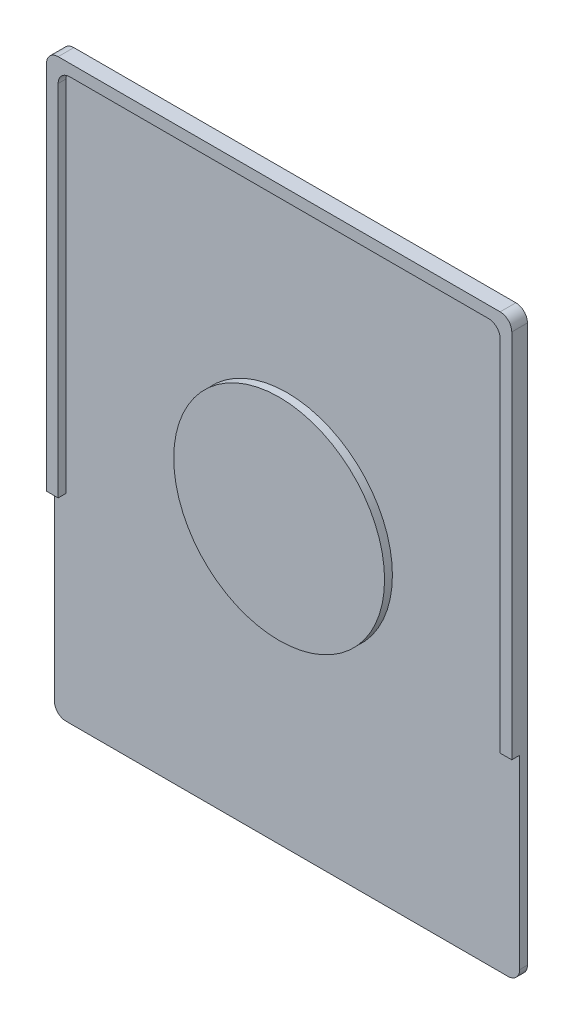
SolidWorks part; units mm, degrees
ref_plane "Front Plane" through (0, 0, 0) normal (0, 0, 1) x (1, 0, 0)
ref_plane "Top Plane" through (0, 0, 0) normal (0, 1, 0) x (1, 0, 0)
ref_plane "Right Plane" through (0, 0, 0) normal (1, 0, 0) x (0, 0, -1)
sketch "Sketch1" plane through (0, 0, 0) normal (0, 0, 1) x (1, 0, 0)
  line L0 (75.9955, -3.6817) -> (75.9955, 195.6023) construction
  line L1 (-0.0045, -3.6817) -> (151.9955, -3.6817)
  line L2 (-4.0045, 0.3183) -> (-4.0045, 191.6023)
  line L3 (-0.0045, 195.6023) -> (151.9955, 195.6023)
  line L4 (155.9955, 0.3183) -> (155.9955, 191.6023)
  line L5 (-4.0045, 95.9603) -> (155.9955, 95.9603) construction
  line L6 (-4.0045, 64.1756) -> (-4.0045, 191.6023)
  line L7 (-0.0045, 195.6023) -> (151.9955, 195.6023)
  line L8 (155.9955, 191.6023) -> (155.9955, 64.1756)
  line L9 (-4.0045, 64.1756) -> (-0.0045, 64.1756)
  line L10 (-0.0045, 64.1756) -> (-0.0045, 187.6023)
  line L11 (3.9955, 191.6023) -> (147.9955, 191.6023)
  line L12 (151.9955, 187.6023) -> (151.9955, 64.1756)
  line L13 (151.9955, 64.1756) -> (155.9955, 64.1756)
  arc A0 (-0.0045, -3.6817) -> (-4.0045, 0.3183) centre (-0.0045, 0.3183) cw
  arc A1 (151.9955, -3.6817) -> (155.9955, 0.3183) centre (151.9955, 0.3183) ccw
  arc A2 (151.9955, 195.6023) -> (155.9955, 191.6023) centre (151.9955, 191.6023) cw
  arc A3 (-4.0045, 191.6023) -> (-0.0045, 195.6023) centre (-0.0045, 191.6023) cw
  circle A4 centre (10.9955, 10.9603) radius 1.495
  circle A5 centre (140.9955, 10.9603) radius 1.495
  circle A6 centre (75.9955, 185.6023) radius 1.495
  circle A7 centre (75.9955, 95.9603) radius 36.25
  circle A8 centre (10.9955, 10.9603) radius 9.6889
  circle A9 centre (140.9955, 10.9603) radius 9.6889
  circle A10 centre (140.9955, 180.9603) radius 9.6889
  circle A11 centre (10.9955, 180.9603) radius 9.6889
  arc A12 (151.9955, 195.6023) -> (155.9955, 191.6023) centre (151.9955, 191.6023) cw
  arc A13 (147.9955, 191.6023) -> (151.9955, 187.6023) centre (147.9955, 187.6023) cw
  arc A14 (-0.0045, 187.6023) -> (3.9955, 191.6023) centre (3.9955, 187.6023) cw
  arc A15 (-4.0045, 191.6023) -> (-0.0045, 195.6023) centre (-0.0045, 191.6023) cw
extrude "Boss-Extrude1" add sketch "Sketch1" against normal blind 2.7 contours L2 A3 L3 A2 L4 A1 L1 A0
extrude "Boss-Extrude2" add sketch "Sketch1<4>" along normal blind 2.7 contours L10 A14 L11 A13 L12 L13 L4 A2 L3 A3 L2 L9 | A7 region at (-1.934, 127.889, 0) region at (75.9955, 95.9603, 0)
sketch "Sketch1<4>" plane through (0, 0, 0) normal (0, 0, 1) x (1, 0, 0) same geometry as "Sketch1"
